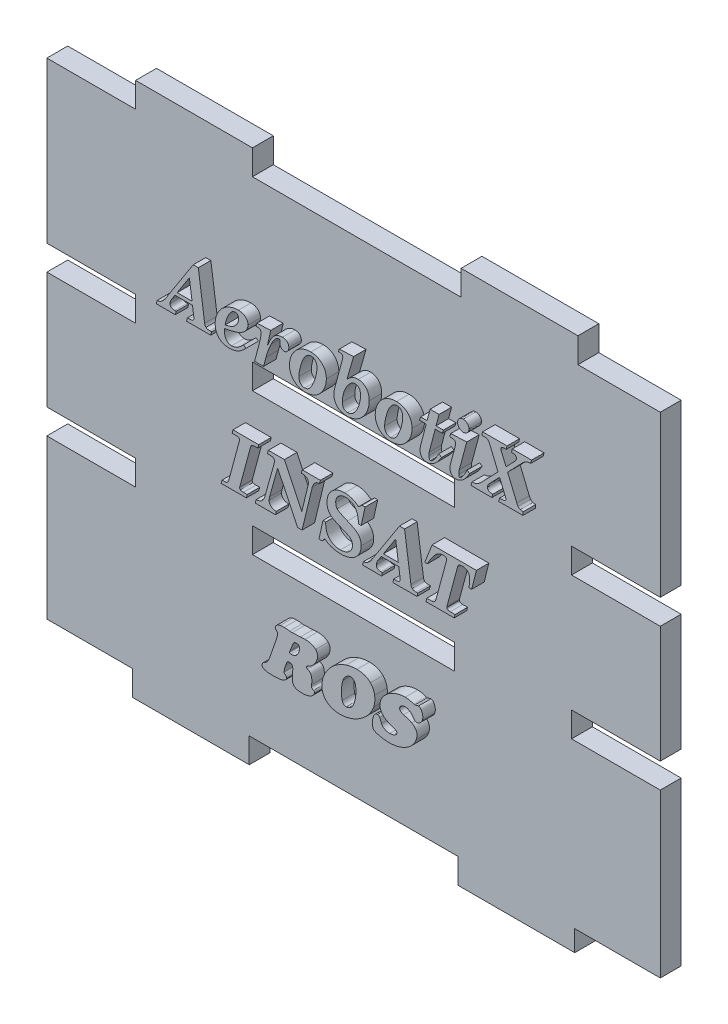
SolidWorks part; units mm, degrees
ref_plane "Front Plane" through (0, 0, 0) normal (0, 0, 1) x (1, 0, 0)
ref_plane "Top Plane" through (0, 0, 0) normal (0, 1, 0) x (1, 0, 0)
ref_plane "Right Plane" through (0, 0, 0) normal (1, 0, 0) x (0, 0, -1)
sketch "Sketch1" plane through (0, 0, 0) normal (0, 0, 1) x (1, 0, 0)
  line L5 (-24, -72.5496) -> (-73.5, -72.5496)
  line L6 (-73.5, 72.5496) -> (73.5, 72.5496)
  line L9 (-73.5, 72.5496) -> (-73.5, -72.5496)
  line L24 (73.5, 72.5496) -> (73.5, -72.5496)
  line L25 (-73.5, 72.5496) -> (73.5, -72.5496) construction
  line L26 (-73.5, -72.5496) -> (73.5, 72.5496) construction
  line L28 (-24, -72.5496) -> (-24, -67.5496)
  line L29 (-24, -67.5496) -> (24, -67.5496)
  line L30 (24, -72.5496) -> (24, -67.5496)
  line L31 (24, -72.5496) -> (73.5, -72.5496)
  line L32 (73.5, 6.4504) -> (73.5, 10.4504) construction
  line L33 (24, -72.5496) -> (-22.4676, -72.5496) construction
  point P0 (0, 0)
  point P5 (0, -67.5496)
  dimension "D1" = 5
  dimension "D2" = 48
extrude "Boss-Extrude1" add sketch "Sketch1" along normal blind 5
sketch "Sketch2" plane through (0, 0, 5) normal (0, 0, 1) x (1, 0, 0)
  line L0 (73.5, -72.5496) -> (73.5, 72.5496) construction
  line L1 (-23.2338, -23.5496) -> (23.2338, -23.5496)
  line L2 (-23.2338, -23.5496) -> (-23.2338, -27.5496)
  line L3 (-23.2338, -27.5496) -> (23.2338, -27.5496)
  line L4 (23.2338, -23.5496) -> (23.2338, -27.5496)
  line L5 (53.2338, -23.5496) -> (73.5, -23.5496)
  line L6 (53.2338, -23.5496) -> (53.2338, -27.3)
  line L7 (53.2338, -27.3) -> (73.5, -27.3)
  line L8 (73.5, -23.5496) -> (73.5, -27.3)
  line L9 (-73.5, -23.5496) -> (-53.2338, -23.5496)
  line L10 (-73.5, -23.5496) -> (-73.5, -27.5496)
  line L11 (-73.5, -27.5496) -> (-53.2338, -27.5496)
  line L12 (-53.2338, -23.5496) -> (-53.2338, -27.5496)
  line L13 (-75, -67.5627) -> (-53.9636, -67.5627)
  line L14 (-75, -67.5627) -> (-75, -72.5496)
  line L15 (-75, -72.5496) -> (-53.9636, -72.5496)
  line L16 (-53.9636, -67.5627) -> (-53.9636, -72.5496)
  line L17 (54, -68.5496) -> (73.5, -68.5496)
  line L18 (54, -68.5496) -> (54, -72.5496)
  line L19 (54, -72.5496) -> (73.5, -72.5496)
  line L20 (73.5, -68.5496) -> (73.5, -72.5496)
  line L21 (-73.5, -72.5496) -> (-24, -72.5496) construction
extrude "Cut-Extrude1" cut sketch "Sketch2" against normal blind 5
sketch "Sketch4" plane through (0, 0, 5) normal (0, 0, 1) x (1, 0, 0)
  line L9 (-73.5, 72.5496) -> (-73.5, -23.5496) construction
  line L20 (24.7662, 54.8659) -> (-23.2338, 54.8659) construction
  line L21 (-73.5, 55.8659) -> (-52.2338, 55.8659)
  line L22 (-73.5, 55.8659) -> (-73.5, 49.8659)
  line L23 (-73.5, 49.8659) -> (-52.2338, 49.8659)
  line L24 (-52.2338, 55.8659) -> (-52.2338, 49.8659)
  line L25 (-24.2338, 55.8659) -> (25.7662, 55.8659)
  line L26 (-24.2338, 55.8659) -> (-24.2338, 49.8659)
  line L27 (-24.2338, 49.8659) -> (25.7662, 49.8659)
  line L28 (25.7662, 55.8659) -> (25.7662, 49.8659)
  line L29 (-23.2338, 54.8659) -> (-23.2338, 50.8659) construction
  line L30 (24.7662, 50.8659) -> (24.7662, 54.8659) construction
  line L31 (73.5, -23.5496) -> (73.5, 72.5496) construction
  line L32 (53.7662, 55.8659) -> (73.5, 55.8659)
  line L33 (53.7662, 55.8659) -> (53.7662, 49.8659)
  line L34 (53.7662, 49.8659) -> (73.5, 49.8659)
  line L35 (73.5, 55.8659) -> (73.5, 49.8659)
  line L36 (74.4146, 54.8659) -> (54.7662, 54.8659) construction
  line L37 (54.7662, 54.8659) -> (54.7662, 50.8659) construction
  line L38 (74.4146, 50.8659) -> (54.7662, 50.8659) construction
  line L39 (-53.2338, 54.8659) -> (-72.8822, 54.8659) construction
  line L40 (-53.2338, 50.8659) -> (-72.8822, 50.8659) construction
  line L41 (-53.2338, 50.8659) -> (-53.2338, 54.8659) construction
  dimension "D1" = 1
  dimension "D2" = 1
  dimension "D3" = 6
  dimension "D4" = 1
  dimension "D5" = 1
  dimension "D6" = 1
  dimension "D7" = 1
  dimension "D8" = 1
  dimension "D9" = 1
  dimension "D10" = 1
extrude "Cut-Extrude2" cut sketch "Sketch4" against normal blind 5
sketch "Sketch5" plane through (0, 0, 5) normal (0, 0, 1) x (1, 0, 0)
  line L0 (-73.5, 14.9882) -> (73.5, 14.9882) construction
  line L1 (-73.5, 49.8659) -> (-73.5, -23.5496) construction
  line L2 (73.5, -23.5496) -> (73.5, 49.8659) construction
  text T0 "      AerobotiX" font "Century Schoolbook" height in points 48
extrude "Boss-Extrude2" add sketch "Sketch5" along normal blind 3
sketch "Sketch6" plane through (0, 0, 5) normal (0, 0, 1) x (1, 0, 0)
  line L0 (-73.5, -14.5115) -> (73.5, -14.5115) construction
  line L1 (-73.5, 49.8659) -> (-73.5, -23.5496) construction
  line L2 (73.5, -23.5496) -> (73.5, 49.8659) construction
  text T0 "         INSAT" font "Century Schoolbook" height in points 48
extrude "Boss-Extrude3" add sketch "Sketch6" along normal blind 3
sketch "Sketch7" plane through (0, 0, 5) normal (0, 0, 1) x (1, 0, 0)
  line L0 (-73.5, 49.8659) -> (-73.5, -23.5496) construction
  line L1 (-73.5, 11.4504) -> (-52.2338, 11.4504)
  line L2 (-73.5, 11.4504) -> (-73.5, 5.4504)
  line L3 (-73.5, 5.4504) -> (-52.2338, 5.4504)
  line L4 (-52.2338, 11.4504) -> (-52.2338, 5.4504)
  line L5 (-73.5, 10.4504) -> (73.5, 10.4504) construction
  line L6 (-53.2338, 6.4504) -> (-53.2338, 10.4504) construction
  line L7 (-73.5, 6.4504) -> (73.5, 6.4504) construction
  line L8 (-73.5, 10.4504) -> (73.5, 10.4504) construction
  line L9 (-24.2338, 11.4504) -> (24.2338, 11.4504)
  line L10 (-24.2338, 11.4504) -> (-24.2338, 5.4504)
  line L11 (-24.2338, 5.4504) -> (24.2338, 5.4504)
  line L12 (24.2338, 11.4504) -> (24.2338, 5.4504)
  line L13 (23.2338, 6.4504) -> (23.2338, 10.4504) construction
  line L14 (-73.5, 6.4504) -> (73.5, 6.4504) construction
  line L15 (-23.2338, 6.4504) -> (-23.2338, 10.4504) construction
  line L16 (73.5, -23.5496) -> (73.5, 49.8659) construction
  line L17 (73.5, 11.4504) -> (52.2338, 11.4504)
  line L18 (73.5, 11.4504) -> (73.5, 5.4504)
  line L19 (73.5, 5.4504) -> (52.2338, 5.4504)
  line L20 (52.2338, 11.4504) -> (52.2338, 5.4504)
  line L21 (-73.5, 10.4504) -> (73.5, 10.4504) construction
  line L22 (53.2338, 6.4504) -> (53.2338, 10.4504) construction
  line L23 (-73.5, 6.4504) -> (73.5, 6.4504) construction
  dimension "D1" = 1
  dimension "D2" = 1
  dimension "D3" = 1
  dimension "D4" = 1
  dimension "D5" = 1
  dimension "D6" = 1
  dimension "D7" = 1
  dimension "D8" = 1
  dimension "D9" = 1
  dimension "D10" = 1
extrude "Cut-Extrude3" cut sketch "Sketch7" against normal blind 5
sketch "Sketch8" plane through (0, 0, 5) normal (0, 0, 1) x (1, 0, 0)
  line L1 (-73.5, 55.8659) -> (73.5, 55.8659)
  line L2 (-73.5, 55.8659) -> (-73.5, 72.5496)
  line L3 (-73.5, 72.5496) -> (73.5, 72.5496)
  line L4 (73.5, 55.8659) -> (73.5, 72.5496)
extrude "Cut-Extrude4" cut sketch "Sketch8" against normal through all
sketch "Sketch9" plane through (0, 0, 5) normal (0, 0, 1) x (1, 0, 0)
  line L0 (73.5, -68.5496) -> (73.5, -27.3) construction
  line L1 (-24.2338, -22.5496) -> (24.2338, -22.5496)
  line L2 (-24.2338, -22.5496) -> (-24.2338, -28.5496)
  line L3 (-24.2338, -28.5496) -> (24.2338, -28.5496)
  line L4 (24.2338, -22.5496) -> (24.2338, -28.5496)
  line L5 (52.2338, -22.5496) -> (73.5, -22.5496)
  line L6 (52.2338, -22.5496) -> (52.2338, -28.5496)
  line L7 (52.2338, -28.5496) -> (73.5, -28.5496)
  line L8 (73.5, -22.5496) -> (73.5, -28.5496)
  line L9 (-73.5, -27.5496) -> (-73.5, -67.5627) construction
  line L10 (-52.2338, -22.5496) -> (-73.5, -22.5496)
  line L11 (-52.2338, -22.5496) -> (-52.2338, -28.5496)
  line L12 (-52.2338, -28.5496) -> (-73.5, -28.5496)
  line L13 (-73.5, -22.5496) -> (-73.5, -28.5496)
  line L14 (-53.2338, -23.5496) -> (-73.5, -23.5496) construction
  line L15 (-53.2338, -27.5496) -> (-53.2338, -23.5496) construction
  line L16 (-73.5, -27.5496) -> (-53.2338, -27.5496) construction
  line L17 (23.2338, -23.5496) -> (-23.2338, -23.5496) construction
  line L18 (-23.2338, -23.5496) -> (-23.2338, -27.5496) construction
  line L19 (-23.2338, -27.5496) -> (23.2338, -27.5496) construction
  line L20 (23.2338, -27.5496) -> (23.2338, -23.5496) construction
  line L21 (73.5, -23.5496) -> (53.2338, -23.5496) construction
  line L22 (53.2338, -23.5496) -> (53.2338, -27.3) construction
  line L23 (-73.5, -27.5496) -> (73.5, -27.5496) construction
  line L30 (53, -72.5496) -> (73.5, -72.5496)
  line L31 (73.5, -72.5496) -> (73.5, -67.5496)
  line L32 (53, -67.5496) -> (53, -72.5496)
  line L33 (73.5, -67.5496) -> (53, -67.5496)
  line L34 (53, -67.5496) -> (53, -72.5496)
  line L35 (73.5, -67.5496) -> (53, -67.5496)
  line L43 (-25, -72.5496) -> (25, -72.5496)
  line L46 (-25, -72.5496) -> (-25, -66.5496)
  line L47 (-25, -66.5496) -> (25, -66.5496)
  line L48 (25, -66.5496) -> (25, -72.5496)
  line L49 (-25, -72.5496) -> (-25, -66.5496)
  line L50 (-25, -66.5496) -> (25, -66.5496)
  line L51 (25, -66.5496) -> (25, -72.5496)
  line L53 (-52.9636, -72.5496) -> (-73.5, -72.5496)
  line L54 (-73.5, -72.5496) -> (-73.5, -66.5627)
  line L55 (-52.9636, -72.5496) -> (-52.9636, -66.5627)
  line L56 (-52.9636, -66.5627) -> (-73.5, -66.5627)
  line L57 (-52.9636, -72.5496) -> (-52.9636, -66.5627)
  line L58 (-52.9636, -66.5627) -> (-73.5, -66.5627)
  dimension "D1" = 1
  dimension "D2" = 1
  dimension "D3" = 1
  dimension "D4" = 1
  dimension "D5" = 1
  dimension "D6" = 1
  dimension "D7" = 1
  dimension "D8" = 1
  dimension "D9" = 1
  dimension "D10" = 1
  dimension "D12" = 1
  dimension "D14" = 1
  dimension "D15" = 1
extrude "Cut-Extrude5" cut sketch "Sketch9" against normal through all
sketch "Sketch10" plane through (0, 0, 5) normal (0, 0, 1) x (1, 0, 0)
  line L0 (-73.5, -48.0496) -> (73.5, -48.0496) construction
  line L1 (-73.5, -28.5496) -> (-73.5, -66.5627) construction
  line L2 (73.5, -67.5496) -> (73.5, -28.5496) construction
  text T0 "             ROS" font "Cooper Black" height in points 48
extrude "Boss-Extrude4" add sketch "Sketch10" along normal blind 3
